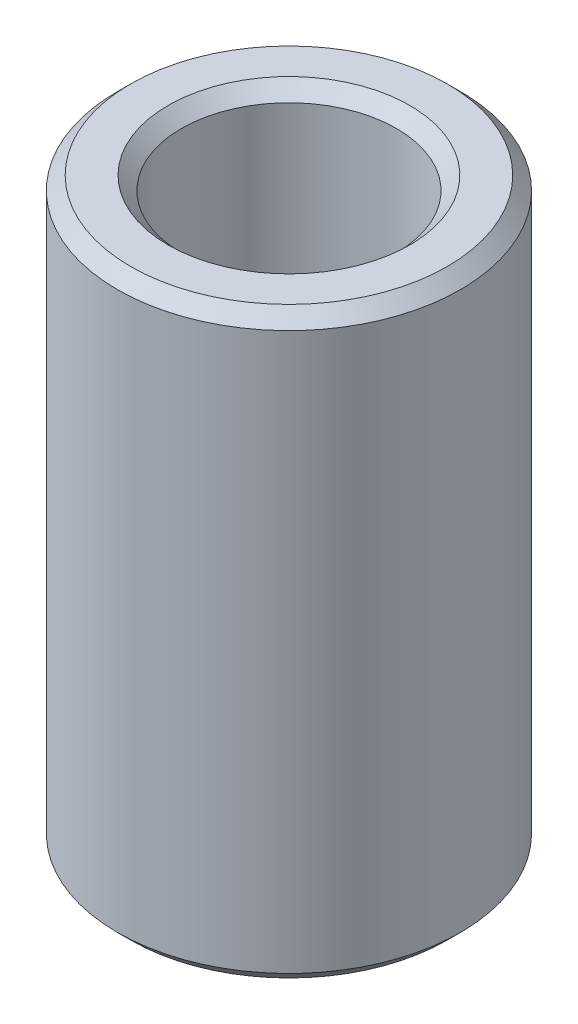
SolidWorks part; units mm, degrees
ref_plane "Front Plane" through (0, 0, 0) normal (0, 0, 1) x (1, 0, 0)
ref_plane "Top Plane" through (0, 0, 0) normal (0, 1, 0) x (1, 0, 0)
ref_plane "Right Plane" through (0, 0, 0) normal (1, 0, 0) x (0, 0, -1)
sketch "Sketch1" plane through (0, 0, 0) normal (0, 1, 0) x (1, 0, 0)
  circle A0 centre (0, 0) radius 27.5
  dimension "SLEEVE_OD" = 55
extrude "Boss-Extrude1" add sketch "Sketch1" along normal blind 93.5069
sketch "Sketch2" plane through (0, 0, 0) normal (0, 1, 0) x (1, 0, 0)
  circle A0 centre (0, 0) radius 17.2434
  dimension "BORE_D" = 34.4868
extrude "Cut-Extrude1" cut sketch "Sketch2" along normal through all
chamfer "Chamfer1" distance 2.1326 angle 45 4 edges at (0, 93.5069, 17.2434) (0, 0, 17.2434) (0, 0, 27.5) (0, 93.5069, 27.5)
